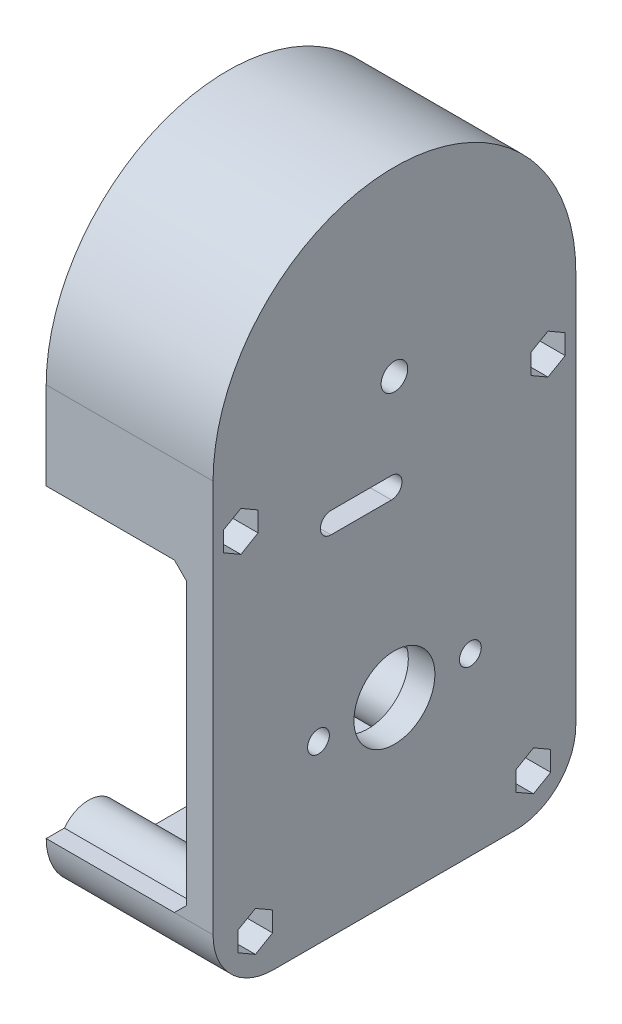
SolidWorks part; units mm, degrees
ref_plane "Front Plane" through (0, 0, 0) normal (0, 0, 1) x (1, 0, 0)
ref_plane "Top Plane" through (0, 0, 0) normal (0, 1, 0) x (1, 0, 0)
ref_plane "Right Plane" through (0, 0, 0) normal (1, 0, 0) x (0, 0, -1)
sketch "Sketch1" plane through (0, 0, 0) normal (1, 0, 0) x (0, 0, -1)
  line L1 (-30, -52.5) -> (30, -52.5)
  line L2 (-30, -52.5) -> (-30, 52.5)
  line L3 (-30, 52.5) -> (30, 52.5)
  line L4 (30, -52.5) -> (30, 52.5)
  line L5 (-30, -52.5) -> (30, 52.5) construction
  line L6 (-30, 52.5) -> (30, -52.5) construction
  point P0 (0, 0)
  dimension "D1" = 105
  dimension "D2" = 60
extrude "Boss-Extrude1" add sketch "Sketch1" along normal blind 4.4
sketch "Sketch2" plane through (4.4, 0, 0) normal (1, 0, 0) x (0, 0, -1)
  line L0 (0, 22.5) -> (0, -23.5) construction
  line L1 (-12.565, -23.5) -> (12.565, -23.5) construction
  line L2 (0, 22.5) -> (0, 52.5) construction
  line L4 (30, 52.5) -> (-30, 52.5) construction
  line L6 (0, 22.5) -> (30, 22.5) construction
  line L7 (30, -52.5) -> (30, 52.5) construction
  circle A0 centre (0, 22.5) radius 2.2
  circle A1 centre (0, -23.5) radius 6.7
  circle A2 centre (-12.565, -23.5) radius 1.8
  circle A3 centre (12.565, -23.5) radius 1.8
  point P4 (0, -0.5)
  point P12 (0, -23.5)
  dimension "D2" = 4.4
  dimension "D3" = 13.4
  dimension "D4" = 3.6
  dimension "D1" = 46
  dimension "D5" = 25.13
extrude "Cut-Extrude1" cut sketch "Sketch2" against normal through all
sketch "Sketch3" plane through (4.4, 0, 0) normal (1, 0, 0) x (0, 0, -1)
  line L0 (-6.1688, 19.7598) -> (-1.2504, 8.6877)
  line L1 (0, -23.5) -> (0, 22.5) construction
  line L2 (-2.8255, 2.9961) -> (-13.4013, -4.4397)
  line L3 (0, 6.8) -> (-5.5, 6.8) construction
  line L5 (0, 6.8) -> (0, -0.2) construction
  line L7 (21.7397, -15.1171) -> (6.298, 24.9285)
  circle A0 centre (0, 22.5) radius 6.75 construction
  circle A1 centre (0, -23.5) radius 23.3 construction
  circle A2 centre (-5.5, 6.8) radius 4.65 construction
  arc A3 (-6.1688, 19.7598) -> (6.298, 24.9285) centre (0, 22.5) cw
  arc A4 (-2.8255, 2.9961) -> (-1.2504, 8.6877) centre (-5.5, 6.8) ccw
  arc A5 (-13.4013, -4.4397) -> (21.7397, -15.1171) centre (0, -23.5) ccw
  point P5 (0.652, 12.2995)
  point P13 (0, 12.2995)
  point P14 (-5.4486, 12.2995)
  dimension "D1" = 46.6
  dimension "D2" = 13.5
  dimension "D4" = 46
  dimension "D5" = 7
  dimension "D3" = 9.3
  dimension "D6" = 5.5
sketch "Sketch4" plane through (4.4, 0, 0) normal (1, 0, 0) x (0, 0, -1)
  line L0 (-10.5, 6.8) -> (-0.5, 6.8) construction
  line L1 (-10.5, 8.55) -> (-0.5, 8.55)
  line L2 (-10.5, 5.05) -> (-0.5, 5.05)
  arc A0 (-10.5, 8.55) -> (-10.5, 5.05) centre (-10.5, 6.8) ccw
  arc A2 (-0.5, 5.05) -> (-0.5, 8.55) centre (-0.5, 6.8) ccw
  point P5 (-5.5, 6.8)
  dimension "D2" = 3.5
  dimension "D3" = 10
extrude "Cut-Extrude2" cut sketch "Sketch4" against normal through all
sketch "Sketch5" plane through (0, 0, 0) normal (-1, 0, 0) x (0, 0, 1)
  circle A0 centre (0, 22.5) radius 4.25
  circle A1 centre (0, 22.5) radius 8
  dimension "D1" = 8.5
  dimension "D2" = 16
extrude "Boss-Extrude2" add sketch "Sketch5" along normal blind 4.3
chamfer "Chamfer1" distance 1 angle 45 1 edges at (0, 22.5, 8)
sketch "Sketch6" plane through (0, 0, 0) normal (-1, 0, 0) x (0, 0, 1)
  line L0 (-30, -52.5) -> (-30, 52.5) construction
  line L1 (-30, 52.5) -> (30, 52.5) construction
  line L2 (30, 52.5) -> (30, -52.5) construction
  line L3 (-30, 22.5) -> (-30, 52.5)
  line L4 (-30, 52.5) -> (0, 52.5)
  line L5 (0, 52.5) -> (-0.1446, 52.7433)
  line L6 (30, 52.5) -> (30, 22.5)
  line L7 (-0.1446, 52.7433) -> (30, 52.5)
  arc A0 (-30, 22.5) -> (0, 52.5) centre (0, 22.5) cw
  arc A1 (30, 22.5) -> (0, 52.5) centre (0, 22.5) ccw
  line M9 (-30, 52.5) -> (-30, -52.5)
  line M11 (30, -52.5) -> (30, 52.5)
  line M12 (30, 52.5) -> (-30, 52.5)
extrude "Cut-Extrude3" cut sketch "Sketch6" against normal through all contours A0 M9 M12 | A1 M11 M12 region at (0, 45.799, 23.299) region at (0, 45.799, -23.299)
sketch "Sketch7" plane through (0, 0, 0) normal (-1, 0, 0) x (0, 0, 1)
  line L0 (-30, 22.5) -> (-30, 8)
  line L2 (-30, -52.5) -> (-30, 22.5) construction
  line L4 (-30, 8) -> (-27, 8)
  line L5 (-27, 22.5) -> (-27, 18)
  line L6 (30, 22.5) -> (30, 8)
  line L7 (-27, 18) -> (-25.4, 18)
  line L8 (-25.4, 8) -> (-27, 8)
  line L9 (30, 22.5) -> (30, -52.5) construction
  line L10 (30, 8) -> (27, 8)
  line L11 (27, 8) -> (25.4, 8)
  line L12 (25.4, 18) -> (27, 18)
  line L13 (27, 18) -> (27, 22.5)
  line L14 (-25.4, 13) -> (25.4, 13) construction
  arc A0 (30, 22.5) -> (-30, 22.5) centre (0, 22.5) ccw construction
  arc A1 (30, 22.5) -> (-30, 22.5) centre (0, 22.5) ccw
  arc A2 (27, 22.5) -> (-27, 22.5) centre (0, 22.5) ccw
  arc A3 (-25.4, 18) -> (-25.4, 8) centre (-25.4, 13) cw
  arc A4 (25.4, 18) -> (25.4, 8) centre (25.4, 13) ccw
  point P21 (0, 52.5)
  dimension "D4" = 5
  dimension "D2" = 4.6
  dimension "D3" = 39.5
  dimension "D1" = 3
extrude "Boss-Extrude3" add sketch "Sketch7" along normal blind 23.2
sketch "Sketch8" plane through (-23.2, 0, 0) normal (-1, 0, 0) x (0, 0, 1)
  circle A0 centre (-25.4, 13) radius 1.8
  circle A1 centre (25.4, 13) radius 1.8
  dimension "D1" = 3.6
extrude "Cut-Extrude4" cut sketch "Sketch8" against normal through all
fillet "Fillet1" radius 10 2 edges at (2.2, -52.5, 30) (2.2, -52.5, -30)
sketch "Sketch10" plane through (0, 0, 0) normal (-1, 0, 0) x (0, 0, 1)
  line L0 (20, -52.5) -> (-20, -52.5) construction
  line L1 (20, -52.5) -> (-20, -52.5)
  line L2 (20, -49.5) -> (-20, -49.5)
  line L3 (-30, -42.5) -> (-27, -42.5)
  line L6 (27, -42.5) -> (30, -42.5)
  line L11 (-23, -45.5) -> (23, -45.5) construction
  arc A0 (20, -52.5) -> (30, -42.5) centre (20, -42.5) ccw construction
  arc A1 (-30, -42.5) -> (-20, -52.5) centre (-20, -42.5) ccw construction
  arc A2 (20, -52.5) -> (30, -42.5) centre (20, -42.5) ccw
  arc A3 (-30, -42.5) -> (-20, -52.5) centre (-20, -42.5) ccw
  arc A4 (-27, -42.5) -> (-20, -49.5) centre (-23, -45.5) cw
  arc A5 (20, -49.5) -> (27, -42.5) centre (23, -45.5) cw
  arc A6 (-27, -42.5) -> (-20, -49.5) centre (-20, -42.5) ccw construction
  arc A7 (20, -49.5) -> (27, -42.5) centre (20, -42.5) ccw construction
  dimension "D2" = 7
  dimension "D1" = 3
extrude "Boss-Extrude4" add sketch "Sketch10" along normal up to surface (23.2 mm away) up to face at (-23.2, 13, 27.2)
sketch "Sketch11" plane through (-23.2, 0, 0) normal (-1, 0, 0) x (0, 0, 1)
  circle A0 centre (-23, -45.5) radius 1.8
  circle A1 centre (23, -45.5) radius 1.8
  dimension "D1" = 3.6
extrude "Cut-Extrude6" cut sketch "Sketch11" against normal through all
sketch "Sketch9" plane through (4.4, 0, 0) normal (1, 0, 0) x (0, 0, -1)
  line L1 (-25.4, 9.7091) -> (-22.55, 11.3546)
  line L2 (-22.55, 11.3546) -> (-22.55, 14.6454)
  line L3 (-22.55, 14.6454) -> (-25.4, 16.2909)
  line L4 (-25.4, 16.2909) -> (-28.25, 14.6454)
  line L5 (-28.25, 14.6454) -> (-28.25, 11.3546)
  line L6 (-28.25, 11.3546) -> (-25.4, 9.7091)
  line L7 (25.4, 9.7091) -> (28.25, 11.3546)
  line L8 (28.25, 11.3546) -> (28.25, 14.6454)
  line L9 (28.25, 14.6454) -> (25.4, 16.2909)
  line L10 (25.4, 16.2909) -> (22.55, 14.6454)
  line L11 (22.55, 14.6454) -> (22.55, 11.3546)
  line L12 (22.55, 11.3546) -> (25.4, 9.7091)
  line L13 (-23, -42.2091) -> (-25.85, -43.8546)
  line L14 (-25.85, -43.8546) -> (-25.85, -47.1454)
  line L15 (-25.85, -47.1454) -> (-23, -48.7909)
  line L16 (-23, -48.7909) -> (-20.15, -47.1454)
  line L17 (-20.15, -47.1454) -> (-20.15, -43.8546)
  line L18 (-20.15, -43.8546) -> (-23, -42.2091)
  line L19 (23, -48.7909) -> (25.85, -47.1454)
  line L20 (25.85, -47.1454) -> (25.85, -43.8546)
  line L21 (25.85, -43.8546) -> (23, -42.2091)
  line L22 (23, -42.2091) -> (20.15, -43.8546)
  line L23 (20.15, -43.8546) -> (20.15, -47.1454)
  line L24 (20.15, -47.1454) -> (23, -48.7909)
  circle A0 centre (-25.4, 13) radius 2.85 construction
  circle A1 centre (25.4, 13) radius 2.85 construction
  circle A2 centre (-23, -45.5) radius 2.85 construction
  circle A3 centre (23, -45.5) radius 2.85 construction
  point P28 (-24.8898, -49.6683)
  point P37 (-24, -43.6813)
  dimension "D1" = 5.7
extrude "Cut-Extrude5" cut sketch "Sketch9" against normal offset from surface (23.6 mm away) 4 up to face at (-23.2, 13, 27.2)
chamfer "Chamfer2" distance 2 angle 45 12 edges at (0, 20.25, -27) (0, 20.25, 27) (0, 49.5, 0) (0, 13, 20.4) (0, 8, 27.7) (0, 13, -20.4) (0, 8, -27.7) (0, -42.5, -28.5) (0, -42.5, 28.5) (0, -41.9645, 19.4645) (0, -41.9645, -19.4645) (0, -49.5, 0)
equation "\"motor_pulley\"=50"
